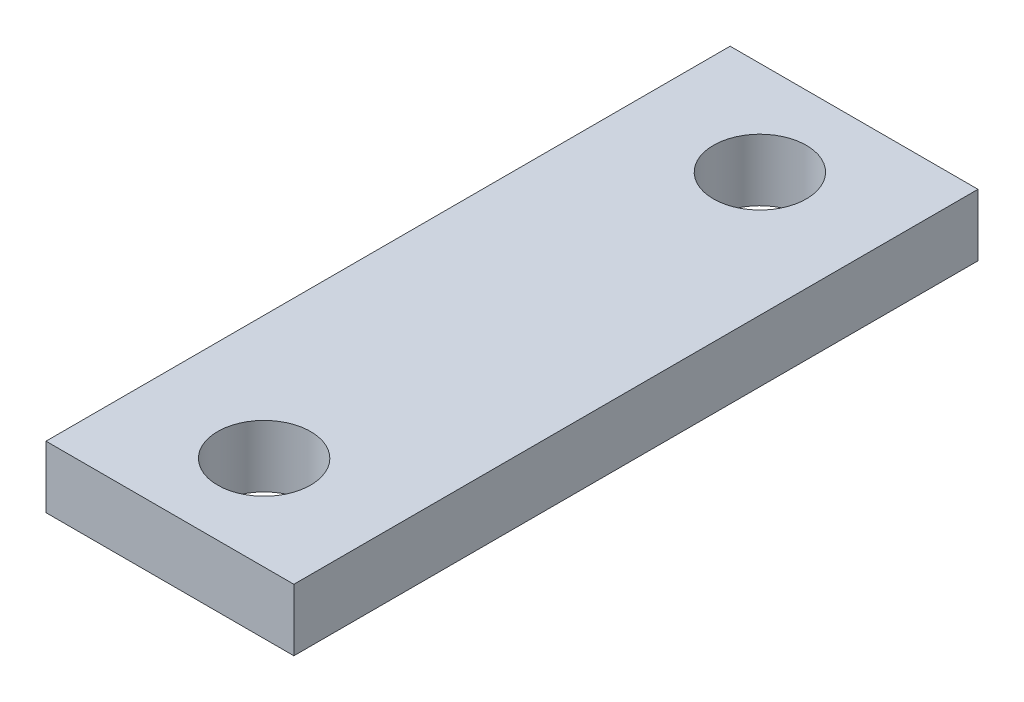
SolidWorks part; units mm, degrees
ref_plane "Front Plane" through (0, 0, 0) normal (0, 0, 1) x (1, 0, 0)
ref_plane "Top Plane" through (0, 0, 0) normal (0, 1, 0) x (1, 0, 0)
ref_plane "Right Plane" through (0, 0, 0) normal (1, 0, 0) x (0, 0, -1)
sketch "Sketch2" plane through (0, 0, 0) normal (0, 1, 0) x (1, 0, 0)
  line L0 (-12.7, 0) -> (12.7, 0) construction
  line L1 (-12.7, 35.052) -> (12.7, 35.052)
  line L2 (-12.7, 35.052) -> (-12.7, -35.052)
  line L3 (-12.7, -35.052) -> (12.7, -35.052)
  line L4 (12.7, 35.052) -> (12.7, -35.052)
  line L5 (0, 25.4) -> (0, -25.4)
  circle A0 centre (0, 25.4) radius 4.7625
  circle A1 centre (0, -25.4) radius 4.7625
  point P10 (0, 0)
  dimension "D3" = 9.525
  dimension "D1" = 25.4
  dimension "D2" = 70.104
  dimension "D4" = 50.8
extrude "Boss-Extrude1" add sketch "Sketch2" along normal blind 6.35 contours L2 L0 A0 L4 L1 | L0 L2 L3 L4 A1 region at (-12.2671, 0, -17.526) region at (-6.35, 0, 0.4329)
equation "\"Lead_Screw_Dist\" = 2in"
equation "\"Lead_Screw_Diam\" = 0.375in"
equation "\"D4@Sketch2\"=\"Lead_Screw_Dist\""
equation "\"D3@Sketch2\"=\"Lead_Screw_Diam\""
